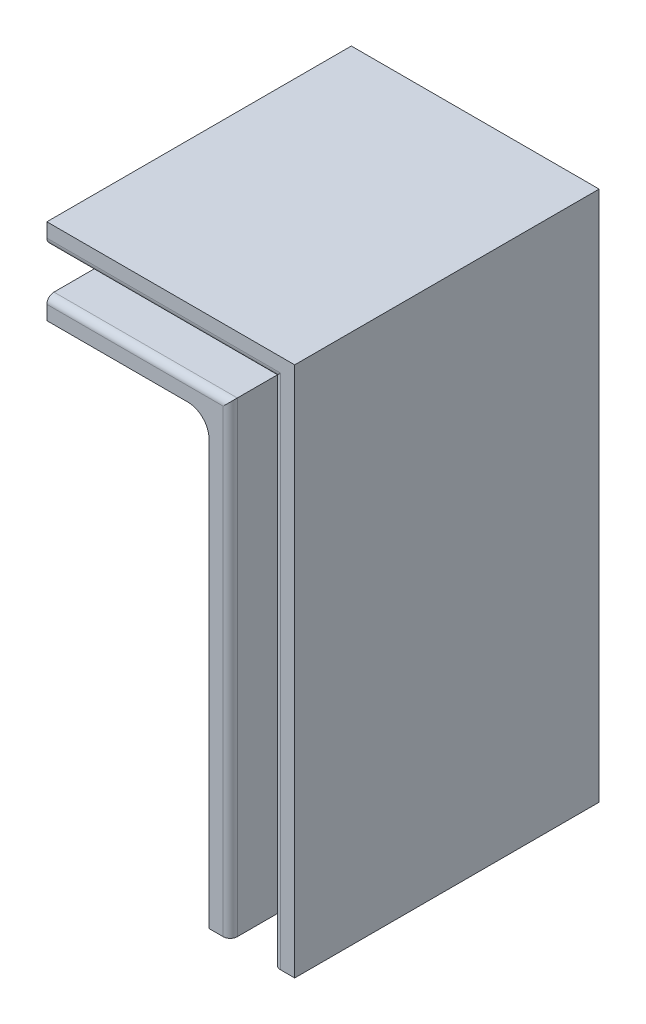
SolidWorks part; units mm, degrees
ref_plane "Front" through (0, 0, 0) normal (0, 0, 1) x (1, 0, 0)
ref_plane "Top" through (0, 0, 0) normal (0, 1, 0) x (1, 0, 0)
ref_plane "Right" through (0, 0, 0) normal (1, 0, 0) x (0, 0, -1)
sketch "Sketch1" plane through (0, 0, 0) normal (0, 0, 1) x (1, 0, 0)
  line L5 (0, 0) -> (35, 0)
  line L6 (0, 0) -> (0, 75)
  line L7 (0, 75) -> (35, 75)
  line L8 (35, 0) -> (35, 75)
  dimension "D1" = 75
  dimension "D2" = 35
extrude "Boss-Extrude1" add sketch "Sketch1" along normal blind 3
sketch "Sketch2" plane through (0, 0, 3) normal (0, 0, 1) x (1, 0, 0)
  line L39 (0, 75) -> (35, 75)
  line L44 (35, 75) -> (35, 0)
  line L45 (35, 0) -> (32, 0)
  line L46 (0, 0) -> (35, 0) construction
  line L47 (32, 0) -> (32, 72)
  line L48 (32, 72) -> (0, 72)
  line L49 (0, 75) -> (0, 0) construction
  line L50 (0, 72) -> (0, 75)
  line L51 (0, 65.9) -> (25.9, 65.9)
  line L52 (25.9, 65.9) -> (25.9, 0)
  line L53 (25.9, 0) -> (22.9, 0)
  line L54 (22.9, 0) -> (22.9, 62.9)
  line L55 (22.9, 62.9) -> (0, 62.9)
  line L56 (0, 62.9) -> (0, 65.9)
  dimension "D1" = 3
  dimension "D2" = 6.1
  dimension "D3" = 6.1
extrude "Boss-Extrude2" add sketch "Sketch2" along normal blind 40
fillet "Fillet1" radius 3 7 edges at (25.9, 32.95, 3) (12.95, 65.9, 3) (16, 72, 3) (22.9, 62.9, 23) (11.45, 62.9, 3) (22.9, 31.45, 3) (32, 36, 3)
fillet "Fillet2" radius 1 4 edges at (12.95, 65.9, 43) (16, 72, 43) (32, 36, 43) (25.9, 32.95, 43)
